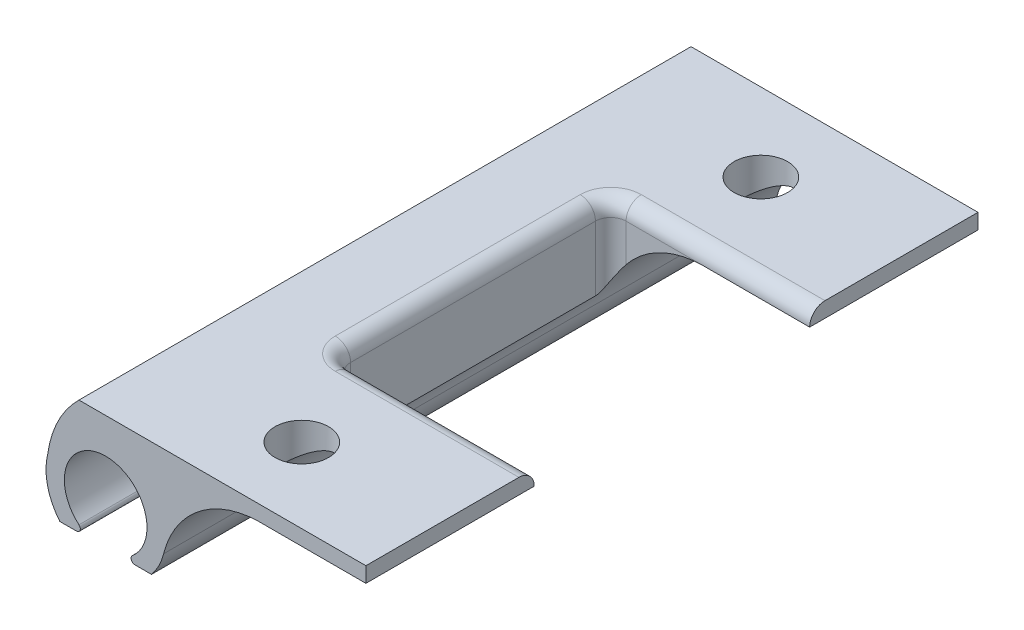
SolidWorks part; units mm, degrees
ref_plane "Front Plane" through (0, 0, 0) normal (0, 0, 1) x (1, 0, 0)
ref_plane "Top Plane" through (0, 0, 0) normal (0, 1, 0) x (1, 0, 0)
ref_plane "Right Plane" through (0, 0, 0) normal (1, 0, 0) x (0, 0, -1)
ref_plane "Плоскость1" through (0, -4, 0) normal (0, 1, 0) x (1, 0, 0)
sketch "Эскиз1" plane through (0, 0, 0) normal (0, 1, 0) x (1, 0, 0)
  line L0 (-40.6, -27.2) -> (40.6, -27.2)
  line L1 (0, 0) -> (44.6, 0) construction
  line L6 (40.6, 27.2) -> (40.6, 23.2) construction
  line L7 (40.6, 27.2) -> (-40.6, 27.2)
  line L11 (-40.6, 27.2) -> (-40.6, 23.2) construction
  line L20 (-44.6, 23.2) -> (-44.6, -23.2)
  line L24 (44.6, -23.2) -> (44.6, 23.2)
  line L51 (-5.4, 27.2) -> (33.6, 27.2)
  arc A0 (-40.6, 27.2) -> (-44.6, 23.2) centre (-40.6, 23.2) ccw
  arc A1 (44.6, 23.2) -> (40.6, 27.2) centre (40.6, 23.2) ccw
  arc A2 (-44.6, -23.2) -> (-40.6, -27.2) centre (-40.6, -23.2) ccw
  arc A3 (40.6, -27.2) -> (44.6, -23.2) centre (40.6, -23.2) ccw
  point P37 (0, 0)
  point P42 (0, 0)
extrude "Бобышка-Вытянуть1" add sketch "Эскиз1" along normal blind 3.9 contours A3 L24 A1 L7 A0 L20 A2 L0 region at (0, 0, 0)
sketch "Эскиз2" plane through (0, -4, 0) normal (0, 1, 0) x (1, 0, 0)
  line L0 (0, 0) -> (0, 45) construction
  line L1 (-45, 45) -> (45, 45) construction
  line L2 (-44.3008, 45) -> (-45, 45) construction
  line L3 (-45, 45) -> (-45, -45) construction
  line L4 (-45, -45) -> (45, -45) construction
  line L5 (45, -45) -> (45, 45) construction
  line L6 (-45, 0) -> (0, 0) construction
  dimension "D1" = 90
  dimension "D2" = 45
  dimension "D3" = 90
  dimension "D4" = 45
sketch "Эскиз3" plane through (0, 0, 0) normal (0, 0, 1) x (1, 0, 0)
  line L0 (-45, -4) -> (45, -4) construction
  line L1 (-45, -4) -> (45, -4) construction
  line L2 (-44.8219, -4) -> (-44.8219, -6.4999) construction
  line L5 (-47.8153, -6.4999) -> (-45.8419, -6.4999)
  line L7 (-43.8019, -6.4999) -> (-41.8285, -6.4999)
  arc A0 (-43.8019, -6.4999) -> (-45.8419, -6.4999) centre (-44.8219, -4) ccw
  arc A1 (-41.8285, -6.4999) -> (-47.8153, -6.4999) centre (-44.8219, -4) ccw
  point P7 (-45.8419, -6.4999)
  point P9 (-43.8019, -6.4999)
  dimension "D1" = 5.4
  dimension "D2" = 7.8
  dimension "D4" = 45
  dimension "D3" = 2.04
  dimension "D5" = 2.9934
  dimension "D6" = 2.4999
extrude "Бобышка-Вытянуть3" add sketch "Эскиз3" along normal mid plane 40
sketch "Эскиз5" plane through (0, 0, 0) normal (0, 0, 1) x (1, 0, 0)
  line L1 (-41.6689, 3.0157) -> (-41.6318, 2.9999)
  line L8 (-45, -4) -> (45, -4) construction
  line L9 (-48.6038, -4.9525) -> (-47.3483, -4.9525)
  line L10 (-42.2954, -4.9525) -> (-41.04, -4.9525)
  line L11 (-36.6416, 0.871) -> (-34.6, 0)
  arc A2 (-42.2954, -4.9525) -> (-47.3483, -4.9525) centre (-44.8219, -4) ccw
  arc A6 (-34.6, 0) -> (-41.04, -4.9525) centre (-34.7077, -6.5233) ccw
  arc A8 (-36.6416, 0.871) -> (-48.6038, -4.9525) centre (-41.6689, -4) ccw
  arc A9 (-43.8019, -6.4999) -> (-45.8419, -6.4999) centre (-44.8219, -4) ccw construction
  arc A10 (-41.8285, -6.4999) -> (-47.8153, -6.4999) centre (-44.8219, -4) ccw construction
  dimension "D1" = 7
  dimension "D2" = 6.5242
  dimension "D3" = 34.7077
  dimension "D4" = 36.6416
extrude "Бобышка-Вытянуть5" add sketch "Эскиз5" along normal mid plane 40 contours L11 A8 L9 A2 L10 A6 region at (-42.3833, -0.3298, 0)
fillet "Скругление1" radius 0.25 2 edges at (-43.8019, -6.4999, 0) (-45.8419, -6.4999, 0)
mirror "Зеркальное отражение1" about plane through (0, 0, 0) normal (1, 0, 0) of "Бобышка-Вытянуть5"
mirror "Зеркальное отражение2" about plane through (0, 0, 0) normal (1, 0, 0) of "Скругление1", "Бобышка-Вытянуть3"
sketch "Эскиз7" plane through (0, 0, 20) normal (0, 0, 1) x (1, 0, 0)
  line L0 (-45, -4) -> (45, -4) construction
  line L1 (49.5, -4) -> (-49.5, -4) construction
  circle A0 centre (-45, -4) radius 5.5
  dimension "D1" = 11
extrude "Вырез-Вытянуть3" cut sketch "Эскиз7" along normal through all
mirror "Зеркальное отражение3" about plane through (0, 0, 0) normal (1, 0, 0) of "Вырез-Вытянуть3" second plane through (0, 0, 0) second plane normal (0, 0, 1)
sketch "Esquisse1" plane through (0, 3.9, 0) normal (0, 1, 0) x (1, 0, 0)
  line L0 (0, 0) -> (0, 45) construction
  line L1 (-44.6, 20) -> (0, 20)
  line L2 (-44.6, 20) -> (-44.6, -20)
  line L3 (-44.6, -20) -> (0, -20)
  line L4 (0, 20) -> (0, -20)
extrude "Enlèv. mat.-Extru.1" cut sketch "Esquisse1" against normal blind 1.54
sketch "Esquisse2" plane through (0, 3.9, 0) normal (0, 1, 0) x (1, 0, 0)
  line L0 (-44.6, 20) -> (-44.6, 27.2)
  line L1 (-44.6, 27.2) -> (51.6, 27.2)
  line L2 (51.6, 27.2) -> (51.6, -27.2)
  line L3 (51.6, -27.2) -> (-44.6, -27.2)
  line L4 (-44.6, -27.2) -> (-44.6, -20)
  line L5 (-44.6, -20) -> (0, -20)
  line L6 (0, -20) -> (0, 20)
  line L7 (0, 20) -> (-44.6, 20)
  line L8 (-40.6, -27.2) -> (40.6, -27.2) construction
  line L10 (40.6, 27.2) -> (-40.6, 27.2) construction
  line L11 (44.6, -23.2) -> (44.6, 23.2) construction
  dimension "D1" = 7
extrude "Enlèv. mat.-Extru.2" cut sketch "Esquisse2" against normal through all
sketch "Esquisse3" plane through (0, 0, 20) normal (0, 0, 1) x (1, 0, 0)
  line L0 (0, 0) -> (0, 2.36) construction
  line L1 (-50, 2.36) -> (0, 2.36)
  line L2 (-50, 2.36) -> (-50, 1)
  line L3 (-50, 1) -> (0, 1)
  line L4 (0, 2.36) -> (0, 1)
  line L5 (0, 0) -> (-34.8154, 0) construction
  line L6 (-44.6, 2.36) -> (0, 2.36) construction
  point P13 (-50, 1.68)
  dimension "D2" = 50
  dimension "D1" = 1
extrude "Enlèv. mat.-Extru.3" cut sketch "Esquisse3" against normal through all
sketch "Esquisse4" plane through (0, 0, 0) normal (0, -1, 0) x (1, 0, 0)
  line L0 (-27.8154, 20) -> (-27.8154, -20)
  line L1 (-27.8154, 20) -> (0, 20)
  line L3 (-27.8154, -20) -> (0, -20)
  line L4 (0, 20) -> (0, -20)
  line L9 (0, 20) -> (-34.8154, 20) construction
  line L10 (-34.8154, -20) -> (0, -20) construction
  line L11 (0, -20) -> (0, 20) construction
  line L12 (-34.8154, 20) -> (-34.8154, -20) construction
  dimension "D1" = 7
extrude "Enlèv. mat.-Extru.4" cut sketch "Esquisse4" against normal through all
sketch "Esquisse5" plane through (0, 1, 0) normal (0, 1, 0) x (1, 0, 0)
  line L0 (-46.5679, 20) -> (-27.8154, 20) construction
  line L1 (-27.8154, -20) -> (-27.8154, 20) construction
  line L2 (-46.5679, -20) -> (-27.8154, -20) construction
  circle A0 centre (-36.9054, 14.9) radius 1.75
  circle A1 centre (-36.9054, -15.1) radius 1.75
  dimension "D1" = 3.5
  dimension "D2" = 3.5
  dimension "D3" = 5.1
  dimension "D4" = 9.09
  dimension "D5" = 9.09
  dimension "D6" = 4.9
extrude "Enlèv. mat.-Extru.5" cut sketch "Esquisse5" against normal through all
sketch "Esquisse6" plane through (0, 1, 0) normal (0, 1, 0) x (1, 0, 0)
  line L0 (-27.8154, -20) -> (-27.8154, 20) construction
  line L1 (-40.8154, 9) -> (-27.8154, 9)
  line L2 (-40.8154, 9) -> (-40.8154, -9)
  line L3 (-40.8154, -9) -> (-27.8154, -9)
  line L4 (-27.8154, 9) -> (-27.8154, -9)
  line L9 (-45, 0) -> (0, 0) construction
  dimension "D1" = 18
  dimension "D2" = 9
  dimension "D3" = 13
extrude "Enlèv. mat.-Extru.6" cut sketch "Esquisse6" against normal through all
fillet "Congé1" radius 1 2 edges at (-40.8154, -1.6149, -9) (-40.8154, -1.6149, 9)
fillet "Congé2" radius 1 5 edges at (-33.8154, 1, -9) (-40.5226, 1, -8.7071) (-33.8154, 1, 9) (-40.5226, 1, 8.7071) (-40.8154, 1, 0)
